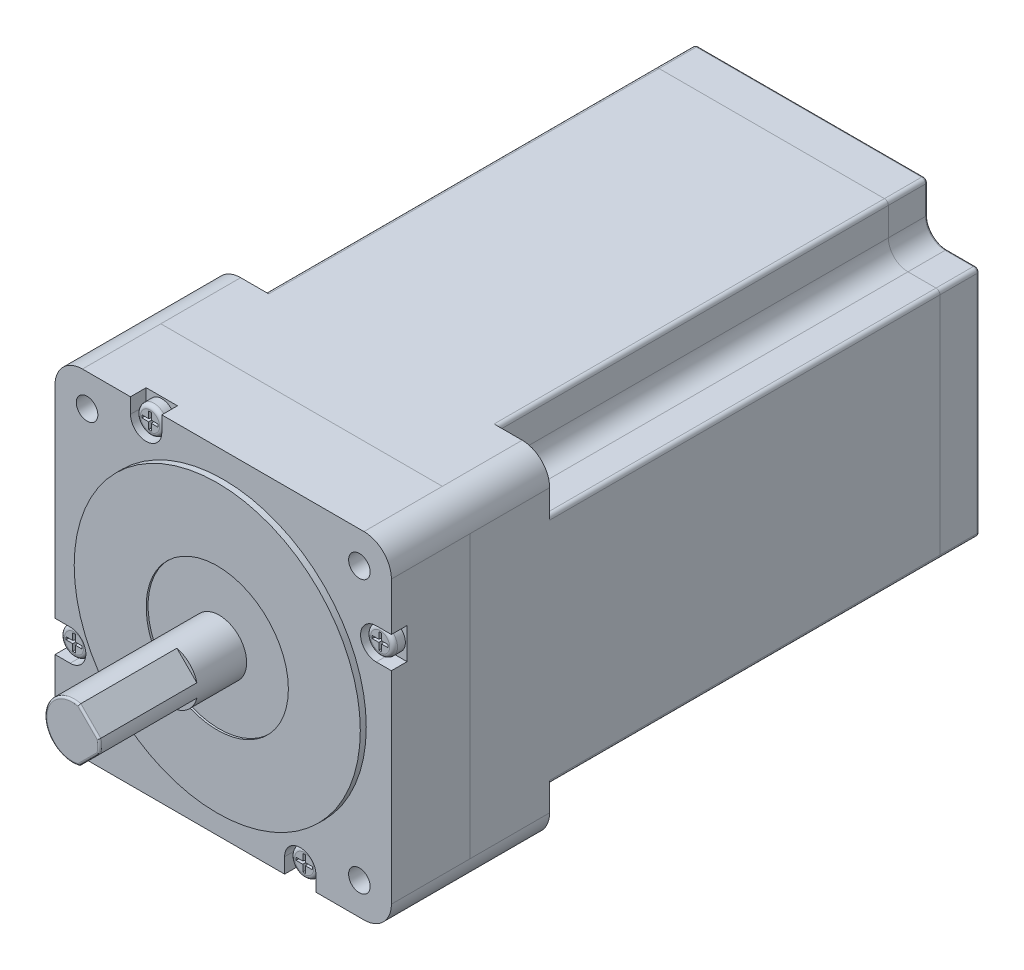
SolidWorks part; units mm, degrees
ref_plane "Front Plane" through (0, 0, 0) normal (0, 0, 1) x (1, 0, 0)
ref_plane "Top Plane" through (0, 0, 0) normal (0, 1, 0) x (1, 0, 0)
ref_plane "Right Plane" through (0, 0, 0) normal (1, 0, 0) x (0, 0, -1)
sketch "Sketch1" plane through (0, 0, 0) normal (0, 0, 1) x (1, 0, 0)
  line L0 (0, 42.925) -> (0, -42.925) construction
  line L1 (-35.925, -42.925) -> (35.925, -42.925)
  line L2 (-42.925, -35.925) -> (-42.925, 35.925)
  line L3 (-35.925, 42.925) -> (35.925, 42.925)
  line L4 (42.925, -35.925) -> (42.925, 35.925)
  line L5 (-42.925, -42.925) -> (42.925, 42.925) construction
  line L6 (-42.925, 42.925) -> (42.925, -42.925) construction
  circle A0 centre (-34.75, 34.75) radius 2.75
  circle A1 centre (34.75, 34.75) radius 2.75
  circle A2 centre (-34.75, -34.75) radius 2.75
  circle A3 centre (34.75, -34.75) radius 2.75
  arc A4 (35.925, -42.925) -> (42.925, -35.925) centre (35.925, -35.925) ccw
  arc A5 (-35.925, -42.925) -> (-42.925, -35.925) centre (-35.925, -35.925) cw
  arc A6 (35.925, 42.925) -> (42.925, 35.925) centre (35.925, 35.925) cw
  arc A7 (-42.925, 35.925) -> (-35.925, 42.925) centre (-35.925, 35.925) cw
  point P0 (0, 0)
  dimension "D3" = 5.5
  dimension "D4" = 69.5
  dimension "D5" = 69.5
  dimension "D6" = 34.75
  dimension "D8" = 7
  dimension "D1" = 85.85
  dimension "D2" = 85.85
  dimension "D7" = 34.75
extrude "Boss-Extrude1" add sketch "Sketch1" along normal blind 150
sketch "Sketch2" plane through (0, 0, 150) normal (0, 0, 1) x (1, 0, 0)
  circle A0 centre (0, 0) radius 36.51
  dimension "D1" = 73.02
extrude "Boss-Extrude2" add sketch "Sketch2" along normal blind 1.52
sketch "Sketch3" plane through (0, 0, 151.52) normal (0, 0, 1) x (1, 0, 0)
  circle A0 centre (0, 0) radius 7
  dimension "D1" = 14
extrude "Boss-Extrude3" add sketch "Sketch3" along normal blind 37 and the other way blind 1 separate body
sketch "Sketch4" plane through (0, 0, 188.52) normal (0, 0, 1) x (1, 0, 0)
  line L0 (0, 0) -> (7, 0) construction
  line L1 (1.6931, 6.7922) -> (6.7922, 1.6931)
  line L2 (1.6931, -6.7922) -> (6.7922, -1.6931)
  circle A0 centre (0, 0) radius 7 construction
  arc A1 (1.6931, 6.7922) -> (6.7922, 1.6931) centre (0, 0) cw
  arc A2 (6.7922, -1.6931) -> (1.6931, -6.7922) centre (0, 0) cw
  dimension "D1" = 13
extrude "Cut-Extrude1" cut sketch "Sketch4" against normal blind 25
fillet "Fillet1" radius 0.5 4 edges at (7, 0, 188.52) (4.2426, -4.2426, 188.52) (4.2426, 4.2426, 188.52) (-7, 0, 188.52)
sketch "Sketch5" plane through (0, 0, 151.52) normal (0, 0, 1) x (1, 0, 0)
  circle A0 centre (0, 0) radius 18.1505
extrude "Cut-Extrude2" cut sketch "Sketch5" against normal blind 0.5
sketch "Sketch6" plane through (0, 0, 0) normal (0, 0, -1) x (-1, 0, 0)
  line L0 (0, 42.925) -> (0, -42.925) construction
  line L1 (-35.925, 42.925) -> (35.925, 42.925) construction
  line L2 (35.925, -42.925) -> (-35.925, -42.925) construction
  line L3 (-42.925, 0) -> (42.925, 0) construction
  line L4 (-42.925, -35.925) -> (-42.925, 35.925) construction
  line L5 (42.925, 35.925) -> (42.925, -35.925) construction
  line L6 (-29.75, 34.75) -> (-29.75, 42.925)
  line L7 (-34.75, 29.75) -> (-42.925, 29.75)
  line L8 (-42.925, 35.925) -> (-42.925, 29.75)
  line L9 (-35.925, 42.925) -> (-29.75, 42.925)
  line L10 (35.925, 42.925) -> (29.75, 42.925)
  line L11 (42.925, 35.925) -> (42.925, 29.75)
  line L12 (34.75, 29.75) -> (42.925, 29.75)
  line L13 (29.75, 34.75) -> (29.75, 42.925)
  line L14 (29.75, -34.75) -> (29.75, -42.925)
  line L15 (34.75, -29.75) -> (42.925, -29.75)
  line L16 (42.925, -35.925) -> (42.925, -29.75)
  line L17 (35.925, -42.925) -> (29.75, -42.925)
  line L18 (-35.925, -42.925) -> (-29.75, -42.925)
  line L19 (-42.925, -35.925) -> (-42.925, -29.75)
  line L20 (-34.75, -29.75) -> (-42.925, -29.75)
  line L21 (-29.75, -34.75) -> (-29.75, -42.925)
  arc A0 (-34.75, 29.75) -> (-29.75, 34.75) centre (-34.75, 34.75) ccw
  arc A2 (-35.925, 42.925) -> (-42.925, 35.925) centre (-35.925, 35.925) ccw
  arc A3 (35.925, 42.925) -> (42.925, 35.925) centre (35.925, 35.925) cw
  arc A4 (34.75, 29.75) -> (29.75, 34.75) centre (34.75, 34.75) cw
  arc A5 (34.75, -29.75) -> (29.75, -34.75) centre (34.75, -34.75) ccw
  arc A6 (35.925, -42.925) -> (42.925, -35.925) centre (35.925, -35.925) ccw
  arc A7 (-35.925, -42.925) -> (-42.925, -35.925) centre (-35.925, -35.925) cw
  arc A8 (-34.75, -29.75) -> (-29.75, -34.75) centre (-34.75, -34.75) cw
  dimension "D1" = 10
extrude "Cut-Extrude3" cut sketch "Sketch6" against normal blind 109.62
sketch "Sketch7" plane through (0, 42.925, 0) normal (0, 1, 0) x (1, 0, 0)
  line L0 (-68.5991, -130) -> (62.7234, -130)
  line L1 (-68.5991, -10) -> (56.8477, -10)
  line L2 (29.75, 0) -> (-29.75, 0) construction
  line L3 (35.925, -150) -> (-35.925, -150) construction
  dimension "D1" = 10
  dimension "D2" = 20
split line "Split Line3"
fillet "Fillet2" radius 0.5 16 edges at (38.8375, 29.75, 0) (31.2145, 31.2145, 0) (29.75, 38.8375, 0) (0, 42.925, 0) (-29.75, 38.8375, 0) (-31.2145, 31.2145, 0) (-38.8375, 29.75, 0) (-42.925, 0, 0) (-38.8375, -29.75, 0) (-31.2145, -31.2145, 0) (-29.75, -38.8375, 0) (0, -42.925, 0) (29.75, -38.8375, 0) (31.2145, -31.2145, 0) (38.8375, -29.75, 0) (42.925, 0, 0)
fillet "Fillet3" radius 1 24 edges at (-29.6036, -42.7786, 0.1464) (-42.7786, -29.6036, 0.1464) (-42.7786, 29.6036, 0.1464) (-29.6036, 42.7786, 0.1464) (29.6036, 42.7786, 0.1464) (42.7786, 29.6036, 0.1464) (42.7786, -29.6036, 0.1464) (29.6036, -42.7786, 0.1464) (29.75, -42.925, 59.81) (29.75, -42.925, 5.25) (42.925, -29.75, 59.81) (42.925, -29.75, 5.25) (42.925, 29.75, 59.81) (42.925, 29.75, 5.25) (29.75, 42.925, 59.81) (29.75, 42.925, 5.25) (-29.75, 42.925, 59.81) (-29.75, 42.925, 5.25) (-42.925, 29.75, 59.81) (-42.925, 29.75, 5.25) (-42.925, -29.75, 59.81) (-42.925, -29.75, 5.25) (-29.75, -42.925, 59.81) (-29.75, -42.925, 5.25)
sketch "Sketch8" plane through (0, 0, 0) normal (0, 0, -1) x (-1, 0, 0)
  circle A0 centre (0, 0) radius 10
  dimension "D1" = 20
extrude "Cut-Extrude4" cut sketch "Sketch8" against normal blind 1
sketch "Sketch9" plane through (0, 0, 1) normal (0, 0, -1) x (-1, 0, 0)
  circle A0 centre (0, 0) radius 6
  dimension "D1" = 12
extrude "Boss-Extrude4" add sketch "Sketch9" along normal blind 0.8 separate body
sketch "Sketch10" plane through (0, 0, 150) normal (0, 0, 1) x (1, 0, 0)
  line L0 (-23.6682, 39.0569) -> (-23.6682, 42.925)
  line L1 (35.925, 42.925) -> (-35.925, 42.925) construction
  line L2 (-23.6682, 42.925) -> (-15.6682, 42.925)
  line L3 (-15.6682, 42.925) -> (-15.6682, 39.0569)
  line L4 (39.0569, 23.6682) -> (42.925, 23.6682)
  line L5 (42.925, 23.6682) -> (42.925, 15.6682)
  line L6 (42.925, 15.6682) -> (39.0569, 15.6682)
  line L7 (23.6682, -39.0569) -> (23.6682, -42.925)
  line L8 (23.6682, -42.925) -> (15.6682, -42.925)
  line L9 (15.6682, -42.925) -> (15.6682, -39.0569)
  line L10 (-39.0569, -23.6682) -> (-42.925, -23.6682)
  line L11 (-42.925, -23.6682) -> (-42.925, -15.6682)
  line L12 (-42.925, -15.6682) -> (-39.0569, -15.6682)
  arc A0 (-23.6682, 39.0569) -> (-15.6682, 39.0569) centre (-19.6682, 39.0569) ccw
  arc A1 (39.0569, 23.6682) -> (39.0569, 15.6682) centre (39.0569, 19.6682) ccw
  arc A2 (23.6682, -39.0569) -> (15.6682, -39.0569) centre (19.6682, -39.0569) ccw
  arc A3 (-39.0569, -23.6682) -> (-39.0569, -15.6682) centre (-39.0569, -19.6682) ccw
  point P25 (0, 0)
  dimension "D1" = 8
  dimension "D2" = 4
extrude "Cut-Extrude5" cut sketch "Sketch10" against normal blind 4
sketch "Sketch11" plane through (0, 0, 146) normal (0, 0, 1) x (1, 0, 0)
  circle A0 centre (-19.6682, 39.0569) radius 3.4342
  point P12 (0, 0)
extrude "Boss-Extrude5" add sketch "Sketch11" along normal blind 3 separate body
fillet "Fillet4" radius 1 1 edges at (-16.234, 39.0569, 149)
sketch "Sketch12" plane through (0, 0, 149) normal (0, 0, 1) x (1, 0, 0)
  line L0 (-19.3179, 39.4068) -> (-17.6111, 39.4068)
  line L1 (-20.0186, 36.9976) -> (-19.3179, 36.9976)
  line L2 (-20.0186, 36.9976) -> (-20.0186, 38.7069)
  line L3 (-20.0186, 41.1161) -> (-19.3179, 41.1161)
  line L4 (-19.3179, 36.9976) -> (-19.3179, 38.7069)
  line L5 (-20.0186, 36.9976) -> (-19.3179, 41.1161) construction
  line L6 (-20.0186, 41.1161) -> (-19.3179, 36.9976) construction
  line L7 (-21.7254, 39.4068) -> (-20.0186, 39.4068)
  line L8 (-21.7254, 39.4068) -> (-21.7254, 38.7069)
  line L9 (-21.7254, 38.7069) -> (-20.0186, 38.7069)
  line L10 (-17.6111, 39.4068) -> (-17.6111, 38.7069)
  line L11 (-21.7254, 39.4068) -> (-17.6111, 38.7069) construction
  line L12 (-21.7254, 38.7069) -> (-17.6111, 39.4068) construction
  line L13 (-19.3179, 38.7069) -> (-17.6111, 38.7069)
  line L14 (-20.0186, 39.4068) -> (-20.0186, 41.1161)
  line L15 (-19.3179, 39.4068) -> (-19.3179, 41.1161)
  point P0 (-19.6682, 39.0569)
  point P6 (-19.6682, 39.0569)
extrude "Cut-Extrude6" cut sketch "Sketch12" against normal blind 2 draft 6
chamfer "Chamfer2" distance 1.5 angle 45 4 edges at (-19.6682, 37.2078, 147) (-19.6682, 40.9059, 147) (-17.8213, 39.0569, 147) (-21.5151, 39.0569, 147) first distance on face at (-19.6682, 37.1027, 148) first distance on face at (-19.6682, 41.011, 148) first distance on face at (-17.7162, 39.0569, 148) first distance on face at (-21.6202, 39.0569, 148)
pattern_circular "CirPattern3" count 4 over 360 about axis through (0, 0, 150) along (0, 0, 1) of bodies 115
